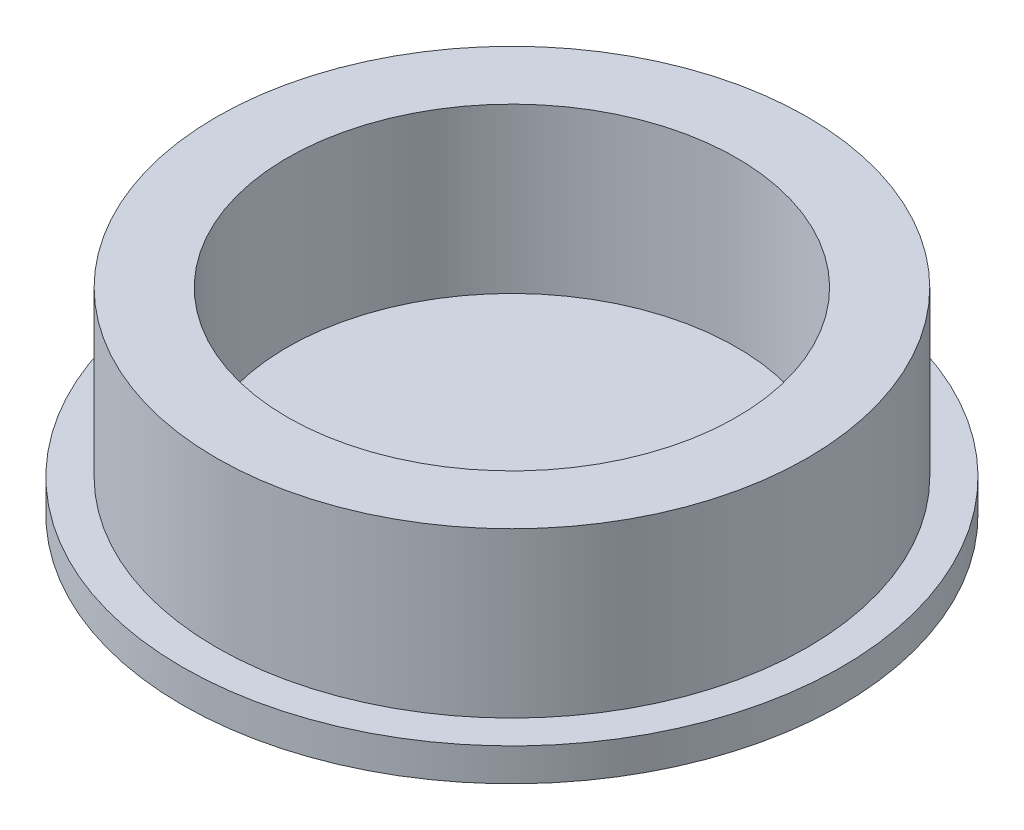
SolidWorks part; units mm, degrees
ref_plane "Front Plane" through (0, 0, 0) normal (0, 0, 1) x (1, 0, 0)
ref_plane "Top Plane" through (0, 0, 0) normal (0, 1, 0) x (1, 0, 0)
ref_plane "Right Plane" through (0, 0, 0) normal (1, 0, 0) x (0, 0, -1)
sketch "Sketch1" plane through (0, 0, 0) normal (0, 1, 0) x (1, 0, 0)
  circle A0 centre (0, 0) radius 10.05
extrude "Boss-Extrude1" add sketch "Sketch1" along normal blind 1
sketch "Sketch2" plane through (0, 1, 0) normal (0, 1, 0) x (1, 0, 0)
  circle A0 centre (0, 0) radius 8.85
  circle A1 centre (0, 0) radius 6.85
extrude "Boss-Extrude2" add sketch "Sketch2" along normal blind 5
sketch "Sketch3" plane through (0, 6, 0) normal (0, 1, 0) x (1, 0, 0)
  circle A0 centre (0, 0) radius 8.95
  circle A1 centre (0, 0) radius 6.85
extrude "Boss-Extrude4" add sketch "Sketch3" against normal up to surface (5 mm away) up to face at (0, 1, 8.85)
sketch "Sketch4" plane through (0, 6, 0) normal (0, 1, 0) x (1, 0, 0)
  circle A0 centre (0, 0) radius 6.85
  circle A1 centre (0, 0) radius 9.01
extrude "Boss-Extrude5" add sketch "Sketch4" against normal up to surface (5 mm away) up to face at (0, 1, 8.95)
